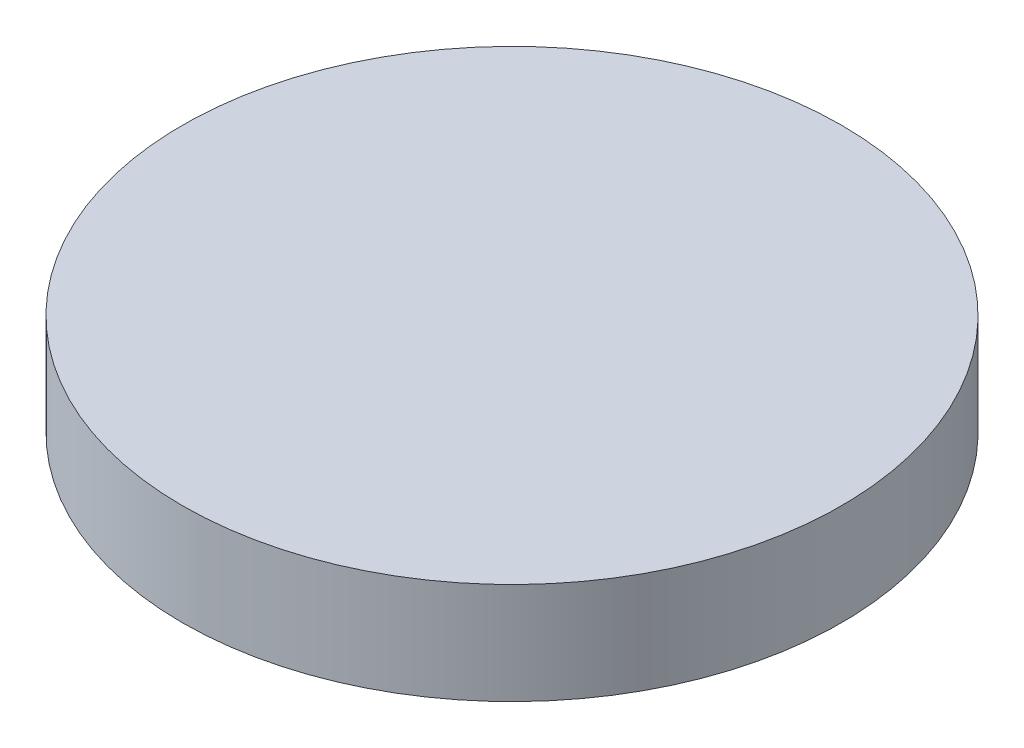
SolidWorks part; units mm, degrees
ref_plane "Alzado" through (0, 0, 0) normal (0, 0, 1) x (1, 0, 0)
ref_plane "Planta" through (0, 0, 0) normal (0, 1, 0) x (1, 0, 0)
ref_plane "Vista lateral" through (0, 0, 0) normal (1, 0, 0) x (0, 0, -1)
sketch "Croquis1" plane through (0, 0, 0) normal (0, 1, 0) x (1, 0, 0)
  circle A0 centre (0, 0) radius 13
  dimension "D1" = 26
extrude "Saliente-Extruir1" add sketch "Croquis1" along normal blind 4
sketch "Croquis2" plane through (0, 0, 0) normal (0, -1, 0) x (1, 0, 0)
  circle A0 centre (0, 0) radius 3.5
  dimension "D1" = 7
extrude "Cortar-Extruir1" cut sketch "Croquis2" against normal blind 0.5
